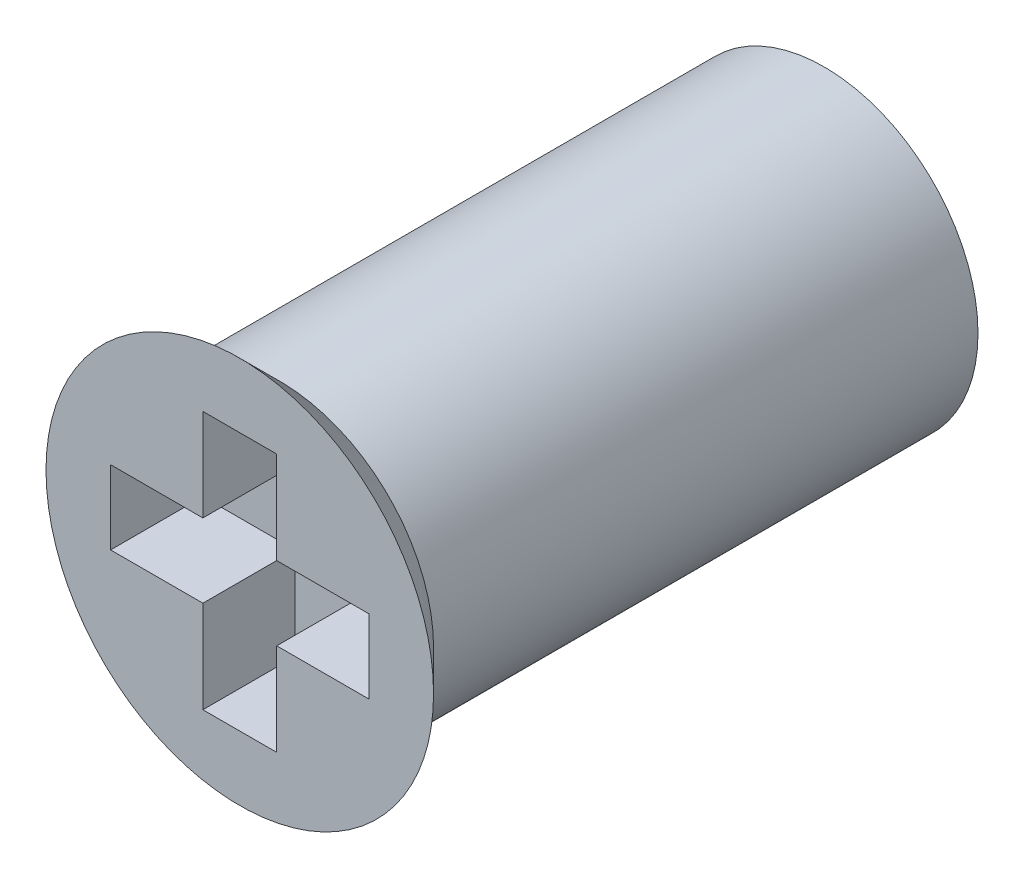
SolidWorks part; units mm, degrees
ref_plane "Plan de face" through (0, 0, 0) normal (0, 0, 1) x (1, 0, 0)
ref_plane "Plan de dessus" through (0, 0, 0) normal (0, 1, 0) x (1, 0, 0)
ref_plane "Plan de droite" through (0, 0, 0) normal (1, 0, 0) x (0, 0, -1)
sketch "Esquisse1" plane through (0, 0, 0) normal (0, 0, 1) x (1, 0, 0)
  circle A0 centre (0, 0) radius 2.5
  dimension "D1" = 5
extrude "Boss.-Extru.1" add sketch "Esquisse1" along normal blind 8
sketch "Esquisse2" plane through (0, 0, 8) normal (0, 0, 1) x (1, 0, 0)
  circle A0 centre (0, 0) radius 3.15
  dimension "D1" = 6.3
extrude "Boss.-Extru.2" add sketch "Esquisse2" along normal blind 1.5
chamfer "Chanfrein1" distance 1.5 angle 45 1 edges at (3.15, 0, 8)
sketch "Esquisse3" plane through (0, 0, 9.5) normal (0, 0, 1) x (1, 0, 0)
  line L0 (-0.6, 2.1) -> (0.6, 2.1)
  line L1 (0.6, 2.1) -> (0.6, 0.6)
  line L2 (0.6, 0.6) -> (2.1, 0.6)
  line L3 (2.1, 0.6) -> (2.1, -0.6)
  line L4 (2.1, -0.6) -> (0.6, -0.6)
  line L5 (0.6, -0.6) -> (0.6, -2.1)
  line L6 (0.6, -2.1) -> (-0.6, -2.1)
  line L7 (-0.6, -2.1) -> (-0.6, -0.6)
  line L8 (-0.6, -0.6) -> (-2.1, -0.6)
  line L9 (-2.1, -0.6) -> (-2.1, 0.6)
  line L10 (-2.1, 0.6) -> (-0.6, 0.6)
  line L11 (-0.6, 0.6) -> (-0.6, 2.1)
  circle A0 centre (0, 0) radius 3.15 construction
  circle A1 centre (0, 0) radius 3.15 construction
  point P17 (0, 2.1)
  point P19 (-2.1, 0)
  dimension "D1" = 1.2
  dimension "D2" = 1.5
extrude "Enlèv. mat.-Extru.1" cut sketch "Esquisse3" against normal blind 1.5
